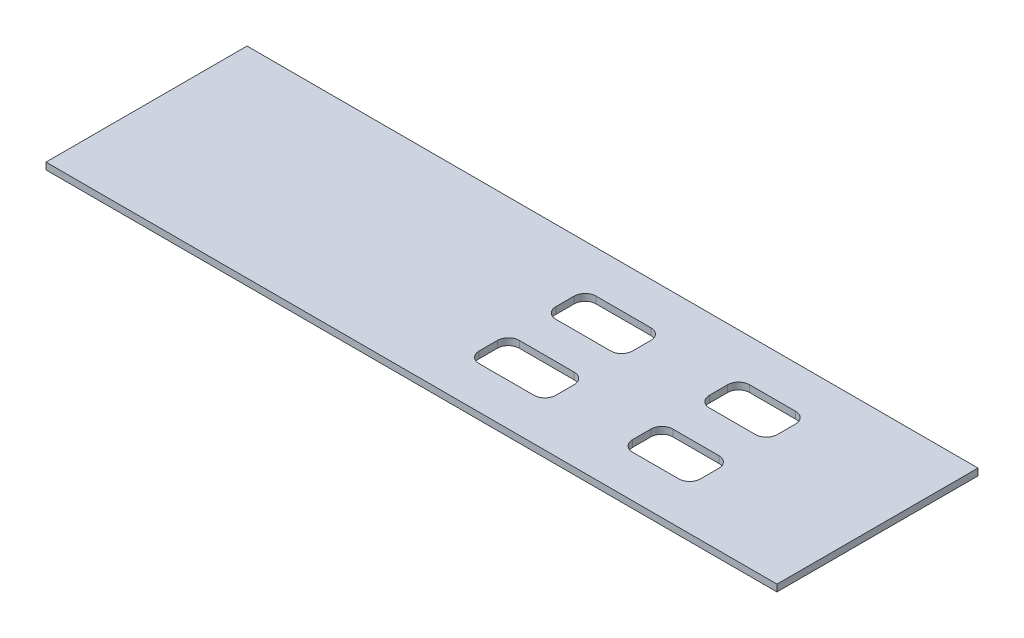
SolidWorks part; units mm, degrees
ref_plane "Front Plane" through (0, 0, 0) normal (0, 0, 1) x (1, 0, 0)
ref_plane "Top Plane" through (0, 0, 0) normal (0, 1, 0) x (1, 0, 0)
ref_plane "Right Plane" through (0, 0, 0) normal (1, 0, 0) x (0, 0, -1)
sketch "Sketch1" plane through (0, 0, 0) normal (0, 1, 0) x (1, 0, 0)
  line L1 (0, 0) -> (152.4, 0)
  line L2 (0, 0) -> (0, 69.85)
  line L3 (0, 69.85) -> (152.4, 69.85)
  line L4 (152.4, 0) -> (152.4, 69.85)
  dimension "D1" = 69.85
  dimension "D2" = 152.4
extrude "Boss-Extrude1" add sketch "Sketch1" along normal blind 2.3622
sketch "Sketch2" plane through (0, 2.3622, 0) normal (0, 1, 0) x (1, 0, 0)
  line L0 (0, 69.85) -> (0, 0) construction
  line L1 (30.48, 55.245) -> (57.15, 55.245)
  line L2 (30.48, 55.245) -> (30.48, 41.275)
  line L3 (30.48, 41.275) -> (57.15, 41.275)
  line L4 (57.15, 55.245) -> (57.15, 41.275)
  line L5 (83.82, 55.245) -> (107.442, 55.245)
  line L6 (83.82, 55.245) -> (83.82, 41.275)
  line L7 (83.82, 41.275) -> (107.442, 41.275)
  line L8 (107.442, 55.245) -> (107.442, 41.275)
  line L9 (152.4, 0) -> (152.4, 69.85) construction
  line L10 (30.48, 28.575) -> (57.15, 28.575)
  line L11 (30.48, 28.575) -> (30.48, 14.605)
  line L12 (30.48, 14.605) -> (57.15, 14.605)
  line L13 (57.15, 28.575) -> (57.15, 14.605)
  line L14 (83.82, 28.575) -> (107.442, 28.575)
  line L15 (83.82, 28.575) -> (83.82, 14.605)
  line L16 (83.82, 14.605) -> (107.442, 14.605)
  line L17 (107.442, 28.575) -> (107.442, 14.605)
  point P10 (83.82, 48.26)
  point P17 (0, 34.925)
  dimension "D1" = 26.67
  dimension "D2" = 23.622
  dimension "D3" = 44.958
  dimension "D4" = 13.97
  dimension "D5" = 12.7
  dimension "D6" = 6.35
  dimension "D7" = 30.48
extrude "Cut-Extrude1" cut sketch "Sketch2" against normal through all
fillet "Fillet1" radius 3.81 16 edges at (83.82, 1.1811, -14.605) (83.82, 1.1811, -41.275) (30.48, 1.1811, -41.275) (30.48, 1.1811, -14.605) (107.442, 1.1811, -14.605) (57.15, 1.1811, -41.275) (57.15, 1.1811, -14.605) (107.442, 1.1811, -41.275) (107.442, 1.1811, -28.575) (107.442, 1.1811, -55.245) (57.15, 1.1811, -28.575) (57.15, 1.1811, -55.245) (30.48, 1.1811, -28.575) (83.82, 1.1811, -28.575) (83.82, 1.1811, -55.245) (30.48, 1.1811, -55.245)
sketch "Sketch4" plane through (0, 0, 0) normal (-1, 0, 0) x (0, 0, 1)
  line L1 (-69.85, 2.3622) -> (0, 2.3622)
  line L2 (-69.85, 2.3622) -> (-69.85, 0)
  line L3 (-69.85, 0) -> (0, 0)
  line L4 (0, 2.3622) -> (0, 0)
extrude "Boss-Extrude2" add sketch "Sketch4" along normal blind 101.6
